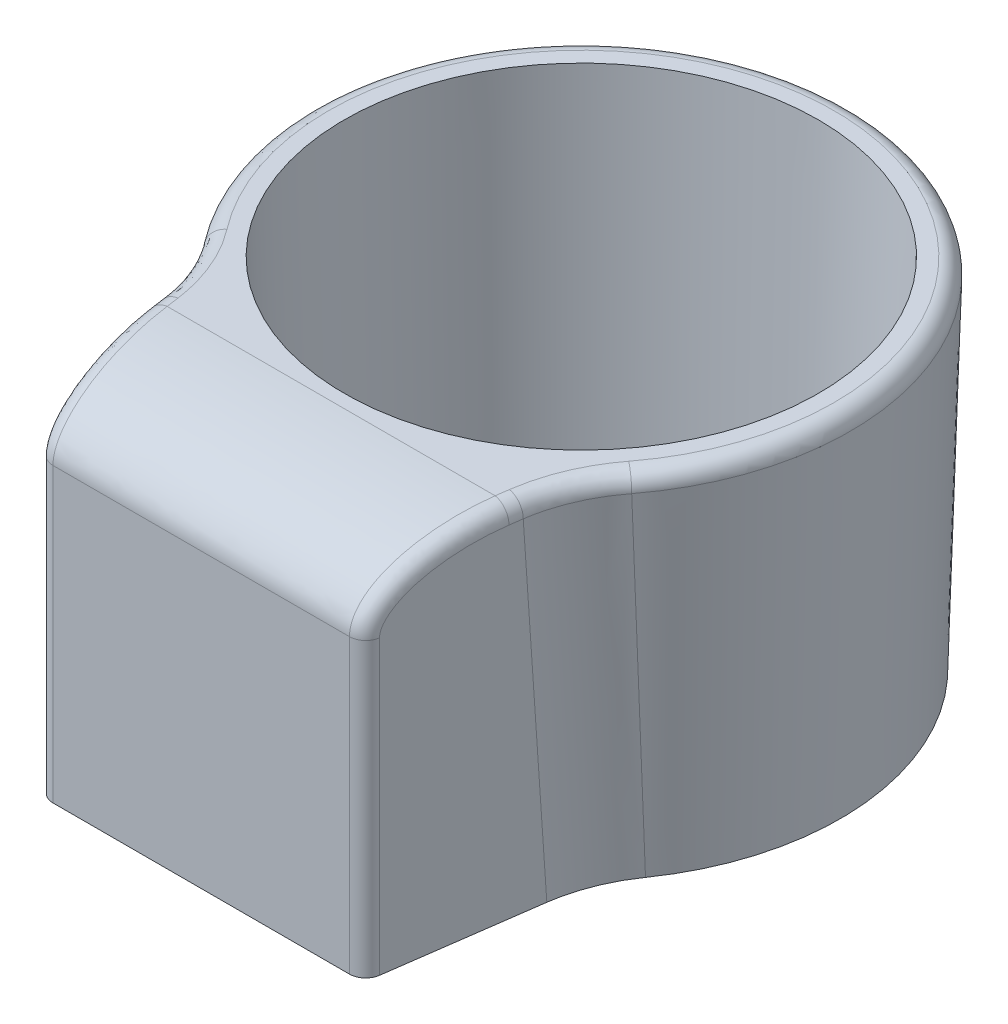
SolidWorks part; units mm, degrees
note: The reader was unsure of these and kept them because the rebuilt part matched: shared geometry of "Sketch4<3>".
ref_plane "Front" through (0, 0, 0) normal (0, 0, 1) x (1, 0, 0)
ref_plane "Top" through (0, 0, 0) normal (0, 1, 0) x (1, 0, 0)
ref_plane "Right" through (0, 0, 0) normal (1, 0, 0) x (0, 0, -1)
sketch "Sketch2" plane through (0, 0, 0) normal (0, 0, 1) x (1, 0, 0)
  line L0 (0, 0) -> (0, 22) construction
  line L1 (0, 0) -> (-15.96, 0) construction
  line L2 (-15.96, 0) -> (-16.6, 22)
  line L3 (-16.6, 22) -> (0, 22) construction
  line L5 (-14.5992, 22) -> (-13.9592, 0)
  line L6 (-15.96, 0) -> (-13.9592, 0)
  line L7 (-16.6, 22) -> (-14.5992, 22)
  dimension "D1" = 15.96
  dimension "D2" = 22
  dimension "D3" = 16.6
  dimension "D4" = 2
revolve "Revolve1" add sketch "Sketch2" angle 360 about L0
sketch "Sketch4" plane through (0, 0, 0) normal (0, 1, 0) x (1, 0, 0)
  line L0 (-11.75, -10.8009) -> (-10, -23.41)
  line L9 (-10, -23.41) -> (10, -23.41)
  line L10 (10, -23.41) -> (11.75, -10.8009)
  line L11 (-10.0094, -12.4312) -> (-8.6938, -21.91)
  line L12 (-8.6938, -21.91) -> (8.6938, -21.91)
  line L13 (8.6938, -21.91) -> (10.0094, -12.4312)
  line L14 (-9.5196, -15.96) -> (9.5196, -15.96) construction
  arc A0 (-10.0094, -12.4312) -> (-11.75, -10.8009) centre (0, 0) cw
  circle A1 centre (0, 0) radius 15.96 construction
  arc A2 (10.0094, -12.4312) -> (11.75, -10.8009) centre (0, 0) ccw
  arc A3 (-10.0094, -12.4312) -> (10.0094, -12.4312) centre (0, 0) ccw
  point P5 (0, -23.41)
  point P9 (0, -21.91)
  point P17 (0, -15.96)
  dimension "D4" = 15.96
  dimension "D5" = 15.96
  dimension "D6" = 20
  dimension "D7" = 23.5
  dimension "D8" = 15.96
  dimension "D1" = 1.5
  dimension "D2" = 1.5
  dimension "D3" = 5.95
extrude "Boss-Extrude1" add sketch "Sketch4" along normal up to surface (22 mm away) up to face at (0, 22, -16.6)
extrude "Cut-Extrude1" cut sketch "Sketch4<3>" along normal offset from surface (20 mm away) 2 up to face at (0, 22, 10.5233)
sketch "Sketch4<3>" plane through (0, 0, 0) normal (0, 1, 0) x (1, 0, 0) same geometry as "Sketch4"
sketch "Sketch5" plane through (0, 20, 0) normal (0, -1, 0) x (1, 0, 0)
  line L1 (8.6938, 21.91) -> (-8.6938, 21.91) construction
  line L2 (-8.6938, 21.91) -> (8.6938, 21.91)
  line L4 (8.6938, 21.91) -> (8.791, 21.21)
  line L5 (10.0094, 12.4312) -> (8.6938, 21.91) construction
  line L6 (8.791, 21.21) -> (-8.791, 21.21)
  line L7 (-8.6938, 21.91) -> (-10.0094, 12.4312) construction
  line L8 (-8.791, 21.21) -> (-8.6938, 21.91)
  point P10 (0, 0)
  point P11 (0, 0)
  dimension "D1" = 0.7
extrude "Boss-Extrude2" add sketch "Sketch5" along normal offset from surface (6.5 mm away) 13.5
sketch "Sketch6" plane through (0, 0, 0) normal (0, -1, 0) x (1, 0, 0)
  line L0 (-9.242, 17.96) -> (-9.0804, 17.96)
  line L1 (-9.0804, 15.96) -> (-9.5196, 15.96)
  line L2 (-9.0804, 17.96) -> (-9.0804, 15.96)
  line L5 (-9.5196, 15.96) -> (-9.242, 17.96)
  line L7 (-10.0094, 12.4312) -> (-8.6938, 21.91) construction
  line L8 (-9.5196, 15.96) -> (9.5196, 15.96)
  line L9 (8.6938, 21.91) -> (10.0094, 12.4312) construction
  arc A0 (10.0094, 12.4312) -> (-10.0094, 12.4312) centre (0, 0) ccw construction
  point P6 (0, 15.96)
  dimension "D1" = 18.6
  dimension "D2" = 2
  dimension "D4" = 19.0392
extrude "Boss-Extrude3" add sketch "Sketch6" against normal blind 10
fillet "Fillet1" radius 10 2 edges
fillet "Fillet3" radius 4 1 edges at (0, 22, 23.41)
fillet "Fillet5" radius 1.5 2 edges at (8.6938, 6.75, 21.91) (-8.6938, 6.75, 21.91)
fillet "Fillet6" radius 1 9 edges at (-11.5957, 22, 13.0844) (0, 22, -16.6) (12.2068, 22, 11.6241)
